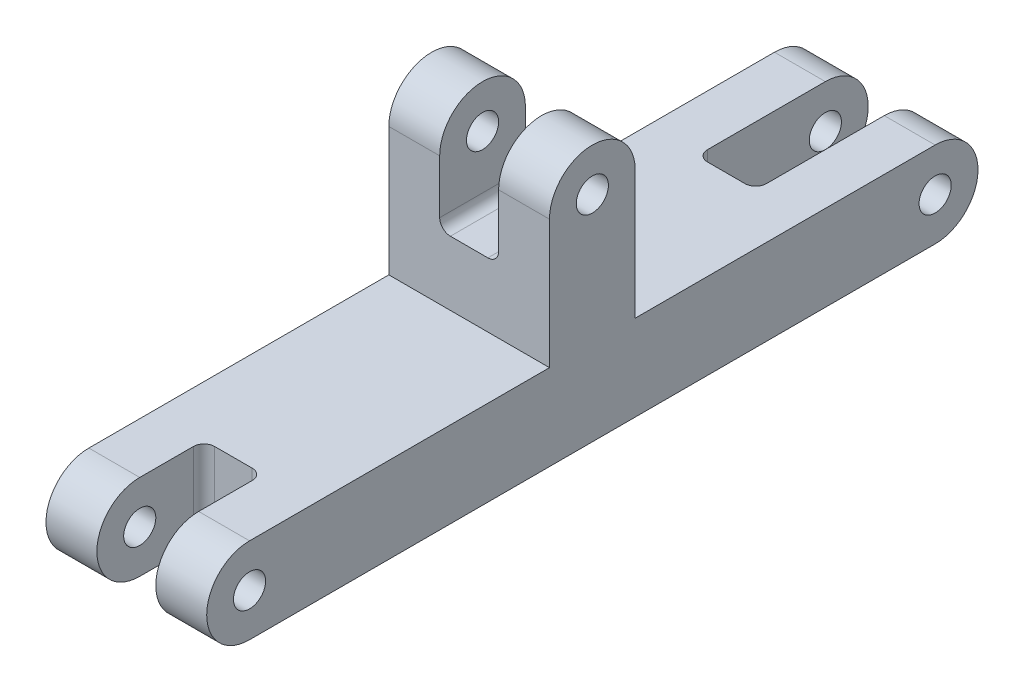
SolidWorks part; units mm, degrees
ref_plane "Alzado" through (0, 0, 0) normal (0, 0, 1) x (1, 0, 0)
ref_plane "Planta" through (0, 0, 0) normal (0, 1, 0) x (1, 0, 0)
ref_plane "Vista lateral" through (0, 0, 0) normal (1, 0, 0) x (0, 0, -1)
sketch "Croquis1" plane through (0, 0, 0) normal (1, 0, 0) x (0, 0, -1)
  line L0 (-15, 0) -> (15, 0) construction
  line L1 (-15, 4) -> (-21, 4) construction
  line L2 (-15, -4) -> (15, -4)
  line L3 (-13, 4) -> (15, 4)
  line L5 (-21, 4) -> (-21, 16)
  line L6 (-21, 16) -> (-13, 16) construction
  line L7 (-13, 4) -> (-13, 16)
  line L8 (-21, 4) -> (-49, 4)
  line L9 (-15, -4) -> (-49, -4)
  line L10 (-49, 4) -> (-49, -4) construction
  arc A0 (-15, 4) -> (-15, -4) centre (-15, 0) ccw construction
  arc A1 (15, -4) -> (15, 4) centre (15, 0) ccw
  circle A2 centre (15, 0) radius 1.5
  arc A3 (-13, 16) -> (-21, 16) centre (-17, 16) ccw
  circle A4 centre (-17, 16) radius 1.5
  circle A5 centre (-15, 0) radius 1.5 construction
  arc A6 (-49, 4) -> (-49, -4) centre (-49, 0) ccw
  circle A7 centre (-49, 0) radius 1.5
  point P3 (0, 0)
  dimension "D2" = 4
  dimension "D3" = 3
  dimension "D4" = 4
  dimension "D7" = 28
  dimension "D1" = 30
  dimension "D5" = 28
  dimension "D6" = 12
extrude "Saliente-Extruir1" add sketch "Croquis1" along normal mid plane 15
sketch "Croquis2" plane through (0, 0, 0) normal (1, 0, 0) x (0, 0, -1)
  line L0 (-21, 16) -> (-21, 4) construction
  line L1 (-21, 10) -> (-13, 10)
  line L2 (-21, 10) -> (-21, 20)
  line L3 (-21, 20) -> (-13, 20)
  line L4 (-13, 10) -> (-13, 20)
  line L5 (-13, 4) -> (-13, 16) construction
  line L11 (-49, -4) -> (15, -4) construction
  line L12 (15, 4) -> (-13, 4) construction
  line L13 (3, 4) -> (19, 4)
  line L14 (3, 4) -> (3, -4)
  line L15 (3, -4) -> (19, -4)
  line L16 (19, 4) -> (19, -4)
  line L18 (-43, 4) -> (-53, 4)
  line L19 (-43, 4) -> (-43, -4)
  line L20 (-43, -4) -> (-53, -4)
  line L21 (-53, 4) -> (-53, -4)
  line L22 (-49, -4) -> (15, -4) construction
  line L23 (-21, 4) -> (-49, 4) construction
  arc A0 (-13, 16) -> (-21, 16) centre (-17, 16) ccw construction
  arc A2 (15, -4) -> (15, 4) centre (15, 0) ccw construction
  arc A5 (-49, 4) -> (-49, -4) centre (-49, 0) ccw construction
  dimension "D5" = 10
  dimension "D1" = 10
  dimension "D3" = 16
extrude "Cortar-Extruir1" cut sketch "Croquis2" against normal mid plane 5.5
fillet "Redondeo1" radius 1 6 edges at (2.75, 0, 43) (-2.75, 0, 43) (2.75, 0, -3) (-2.75, 0, -3) (2.75, 10, 17) (-2.75, 10, 17)
